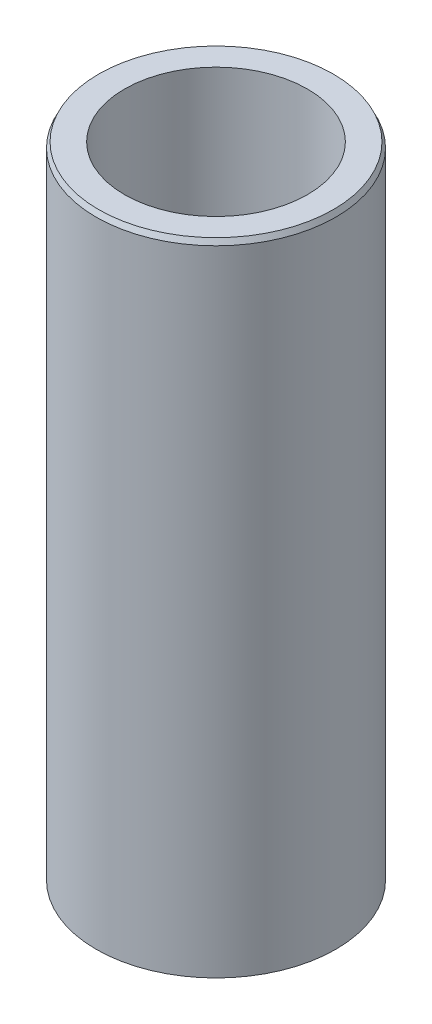
SolidWorks part; units mm, degrees
ref_plane "Front Plane" through (0, 0, 0) normal (0, 0, 1) x (1, 0, 0)
ref_plane "Top Plane" through (0, 0, 0) normal (0, 1, 0) x (1, 0, 0)
ref_plane "Right Plane" through (0, 0, 0) normal (1, 0, 0) x (0, 0, -1)
sketch "Sketch1" plane through (0, 0, 0) normal (0, 1, 0) x (1, 0, 0)
  circle A0 centre (0, 0) radius 40
  dimension "SHAFT_OD" = 80
extrude "Boss-Extrude1" add sketch "Sketch1" along normal blind 214.1818
sketch "Sketch2" plane through (0, 0, 0) normal (0, 1, 0) x (1, 0, 0)
  circle A0 centre (0, 0) radius 30.5337
  dimension "BORE_D" = 61.0674
extrude "Cut-Extrude1" cut sketch "Sketch2" along normal through all
chamfer "Chamfer1" distance 1.767 angle 25.352 2 edges at (0, 214.1818, 40) (0, 0, 40) first distance on face at (0, 214.1818, 40) first distance on face at (0, 0, 30.5337)
